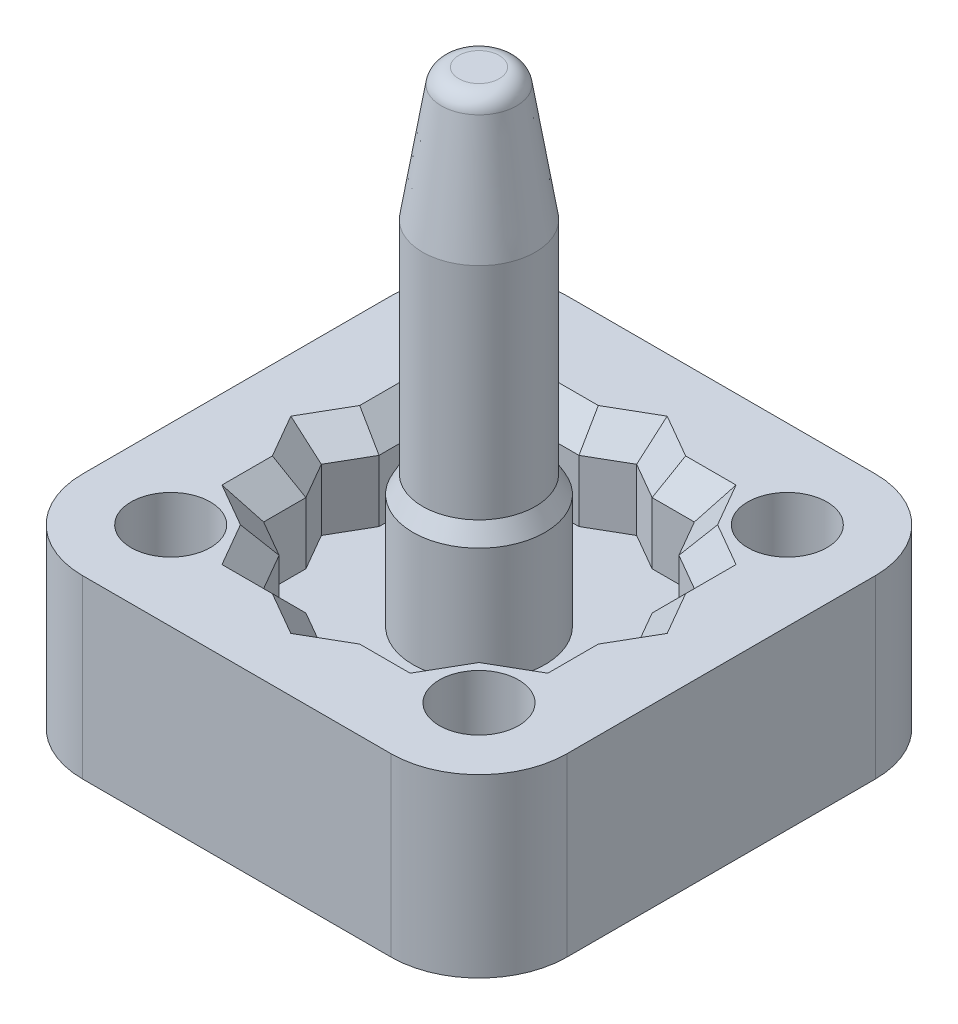
SolidWorks part; units mm, degrees
ref_plane "Front Plane" through (0, 0, 0) normal (0, 0, 1) x (1, 0, 0)
ref_plane "Top Plane" through (0, 0, 0) normal (0, 1, 0) x (1, 0, 0)
ref_plane "Right Plane" through (0, 0, 0) normal (1, 0, 0) x (0, 0, -1)
sketch "Sketch1" plane through (0, 0, 0) normal (0, 0, 1) x (1, 0, 0)
  line L0 (0, 27.5) -> (0, -27.5) construction
  line L1 (0, 27.5) -> (2.2946, 27.5)
  line L2 (4.2694, 25.816) -> (6.4, 12.5)
  line L3 (6.4, 12.5) -> (6.4, -12.5)
  line L4 (6.4, -27.5) -> (0, -27.5)
  line L5 (0, 27.5) -> (0, -27.5)
  line L6 (6.4, -12.5) -> (7.5, -12.5)
  line L7 (7.5, -12.5) -> (7.5, -27.5)
  line L8 (7.5, -27.5) -> (6.4, -27.5)
  arc A0 (2.2946, 27.5) -> (4.2694, 25.816) centre (2.2946, 25.5) cw
  point P4 (0, 0)
  point P10 (4, 27.5)
  dimension "D5" = 2
  dimension "D1" = 40
  dimension "D2" = 15
  dimension "D3" = 12.8
  dimension "D4" = 4
  dimension "D6" = 7.5
  dimension "D7" = 15
revolve "Revolve1" add sketch "Sketch1" angle 360 about L0
sketch "Sketch2" plane through (0, -27.5, 0) normal (0, -1, 0) x (1, 0, 0)
  line L0 (27.5, 27.5) -> (-27.5, -27.5) construction
  line L1 (17.5, 27.5) -> (-17.5, 27.5)
  line L2 (27.5, 17.5) -> (27.5, -17.5)
  line L3 (17.5, -27.5) -> (-17.5, -27.5)
  line L4 (-27.5, 17.5) -> (-27.5, -17.5)
  arc A0 (-17.5, 27.5) -> (-27.5, 17.5) centre (-17.5, 17.5) ccw
  arc A1 (-17.5, -27.5) -> (-27.5, -17.5) centre (-17.5, -17.5) cw
  arc A2 (27.5, -17.5) -> (17.5, -27.5) centre (17.5, -17.5) cw
  arc A3 (17.5, 27.5) -> (27.5, 17.5) centre (17.5, 17.5) cw
  dimension "D2" = 10
  dimension "D1" = 55
extrude "Boss-Extrude1" add sketch "Sketch2" along normal blind 10
sketch "Sketch3" plane through (0, -27.5, 0) normal (0, 1, 0) x (1, 0, 0)
  circle A0 centre (-17.5, 17.5) radius 4.5
  dimension "D1" = 9
extrude "Cut-Extrude1" cut sketch "Sketch3" against normal through all
mirror "Mirror1" about plane through (0, 0, 0) normal (0, 0, 1) of "Cut-Extrude1" second plane through (0, 0, 0) second plane normal (1, 0, 0)
sketch "Sketch4" plane through (0, -27.5, 0) normal (0, 1, 0) x (1, 0, 0)
  line L0 (17.5, -27.5) -> (-17.5, -27.5) construction
  line L1 (-17.5, 27.5) -> (17.5, 27.5)
  line L2 (-27.5, 17.5) -> (-27.5, -17.5)
  line L3 (-17.5, -27.5) -> (17.5, -27.5)
  line L4 (27.5, 17.5) -> (27.5, -17.5)
  line L5 (27.5, 17.5) -> (27.5, -17.5) construction
  line L6 (-17.5, 27.5) -> (17.5, 27.5) construction
  line L7 (-27.5, -17.5) -> (-27.5, 17.5) construction
  arc A0 (17.5, 27.5) -> (27.5, 17.5) centre (17.5, 17.5) cw
  arc A1 (17.5, -27.5) -> (27.5, -17.5) centre (17.5, -17.5) ccw
  arc A2 (-27.5, -17.5) -> (-17.5, -27.5) centre (-17.5, -17.5) ccw
  arc A3 (-17.5, 27.5) -> (-27.5, 17.5) centre (-17.5, 17.5) ccw
  circle A5 centre (-17.5, 17.5) radius 4.5
  circle A6 centre (17.5, 17.5) radius 4.5
  circle A7 centre (17.5, -17.5) radius 4.5
  circle A8 centre (-17.5, -17.5) radius 4.5
  dimension "D3" = 9
extrude "Boss-Extrude2" add sketch "Sketch4" along normal blind 10
chamfer "Chamfer2" distance 2 distance2 1.1 1 edges at (0, -12.5, 7.5) first distance on face at (0, -12.5, 7.5)
sketch "Sketch5" plane through (0, -17.5, 0) normal (0, 1, 0) x (1, 0, 0)
  line L1 (17.8979, 0) -> (8.9489, 15.5)
  line L2 (8.9489, 15.5) -> (-8.9489, 15.5)
  line L3 (-8.9489, 15.5) -> (-17.8979, 0)
  line L4 (-17.8979, 0) -> (-8.9489, -15.5)
  line L5 (-8.9489, -15.5) -> (8.9489, -15.5)
  line L6 (8.9489, -15.5) -> (17.8979, 0)
  circle A0 centre (0, 0) radius 15.5 construction
  circle A1 centre (0, 0) radius 7.5 construction
  circle A2 centre (0, 0) radius 7.5
  point P12 (0, 0)
  dimension "D1" = 31
extrude "Cut-Extrude2" cut sketch "Sketch5" against normal blind 10
sketch "Sketch6" plane through (0, -17.5, 0) normal (0, 1, 0) x (1, 0, 0)
  line L1 (15.5, -8.9489) -> (15.5, 8.9489)
  line L2 (15.5, 8.9489) -> (0, 17.8979)
  line L3 (0, 17.8979) -> (-15.5, 8.9489)
  line L4 (-15.5, 8.9489) -> (-15.5, -8.9489)
  line L5 (-15.5, -8.9489) -> (0, -17.8979)
  line L6 (0, -17.8979) -> (15.5, -8.9489)
  circle A0 centre (0, 0) radius 15.5 construction
  circle A1 centre (0, 0) radius 7.5 construction
  circle A2 centre (0, 0) radius 7.5
  point P1 (18.5801, -8.9107)
  dimension "D1" = 31
extrude "Cut-Extrude4" cut sketch "Sketch6" against normal up to surface (10 mm away) up to face at (0, -27.5, 7.5)
chamfer "Chamfer3" distance 3 angle 45 24 edges at (10.1479, -17.5, -13.4234) (6.5511, -17.5, -15.5) (2.0766, -17.5, -16.6989) (-2.0766, -17.5, -16.6989) (-6.5511, -17.5, -15.5) (-10.1479, -17.5, -13.4234) (-13.4234, -17.5, -10.1479) (-15.5, -17.5, -6.5511) (-16.6989, -17.5, -2.0766) (-16.6989, -17.5, 2.0766) (-15.5, -17.5, 6.5511) (-13.4234, -17.5, 10.1479) (-10.1479, -17.5, 13.4234) (-6.5511, -17.5, 15.5) (-2.0766, -17.5, 16.6989) (2.0766, -17.5, 16.6989) (6.5511, -17.5, 15.5) (10.1479, -17.5, 13.4234) (13.4234, -17.5, 10.1479) (15.5, -17.5, 6.5511) (16.6989, -17.5, 2.0766) (16.6989, -17.5, -2.0766) (15.5, -17.5, -6.5511) (13.4234, -17.5, -10.1479)
